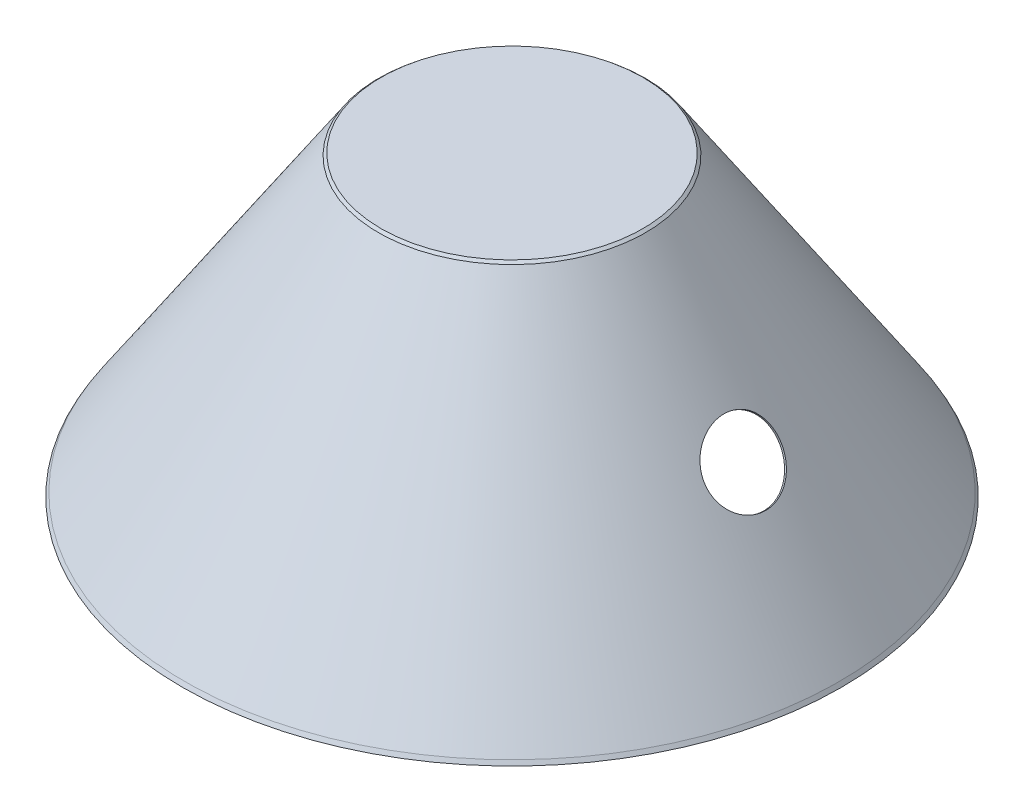
SolidWorks part; units mm, degrees
material "Alumina"
ref_plane "Front Plane" through (0, 0, 0) normal (0, 0, 1) x (1, 0, 0)
ref_plane "Top Plane" through (0, 0, 0) normal (0, 1, 0) x (1, 0, 0)
ref_plane "Right Plane" through (0, 0, 0) normal (1, 0, 0) x (0, 0, -1)
sketch "Sketch1" plane through (0, 0, 0) normal (0, 0, 1) x (1, 0, 0)
  line L0 (0, 0) -> (0, 2000) construction
  line L2 (0, 2000) -> (598.217, 2000)
  line L4 (1495.54, 650) -> (598.217, 2000)
  line L5 (0, 0) -> (0, -10) construction
  line L6 (1495.54, 0) -> (1505.54, 0) construction
  line L7 (1505.54, 0) -> (1505.54, -10) construction
  line L10 (0, 2000) -> (0, 2010) construction
  line L11 (598.217, 2000) -> (598.217, 2010) construction
  line L12 (0, 2010) -> (598.217, 2010)
  line L13 (1046.8785, 1325) -> (1055.2066, 1330.5356) construction
  line L14 (1055.2066, 1330.5356) -> (610.2245, 2000)
  line L15 (610.2245, 2000) -> (598.217, 2010)
  line L16 (1055.2066, 1330.5356) -> (1495.54, 668.065)
  line L17 (1495.54, 668.065) -> (1505.54, 650)
  line L18 (0, 2010) -> (0, 2000)
  line L20 (1505.54, 650) -> (1495.54, 650)
revolve "Revolve1" add sketch "Sketch1" angle 360 about L0
ref_plane "Plane1" through (1345.2531, 894.1678, 0) normal (0.8328, 0.5536, 0) x (0, 0, -1)
sketch "Sketch2" plane through (1345.2531, 894.1678, 0) normal (0.8328, 0.5536, 0) x (0, 0, -1)
  circle A0 centre (0, 509.8762) radius 172.204
extrude "Cut-Extrude1" cut sketch "Sketch2" against normal through all
pattern_circular "CirPattern1" count 2 every 180 of "Cut-Extrude1"
